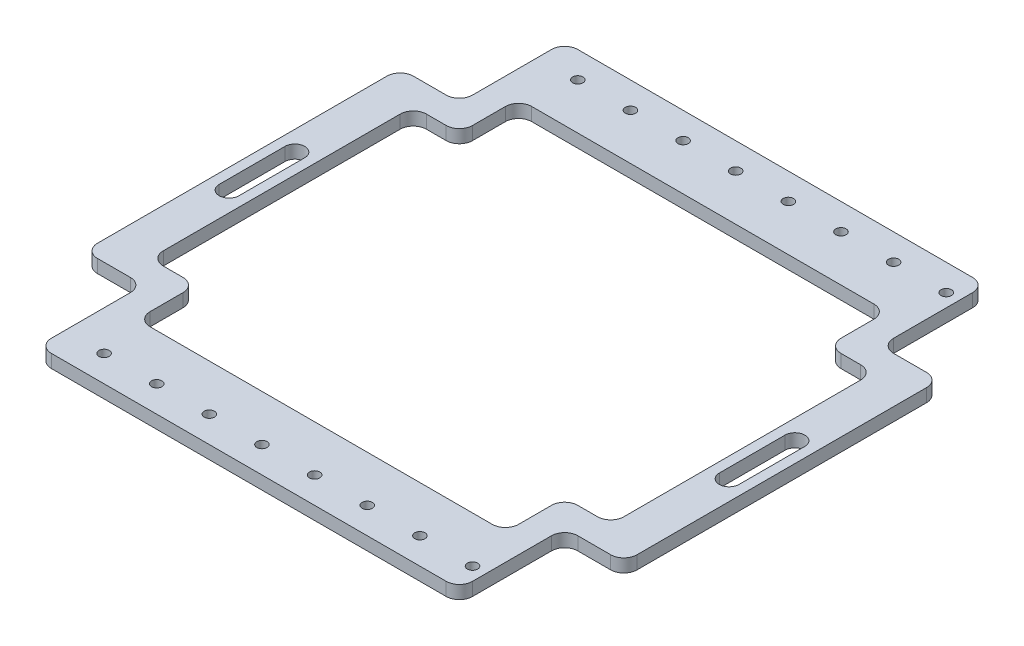
SolidWorks part; units mm, degrees
material "PC High Viscosity"
ref_plane "Front Plane" through (0, 0, 0) normal (0, 0, 1) x (1, 0, 0)
ref_plane "Top Plane" through (0, 0, 0) normal (0, 1, 0) x (1, 0, 0)
ref_plane "Right Plane" through (0, 0, 0) normal (1, 0, 0) x (0, 0, -1)
sketch "Sketch1" plane through (0, 0, 0) normal (0, 1, 0) x (1, 0, 0)
  line L0 (0, 0) -> (0, 50.8)
  line L5 (0, 50.8) -> (-28.575, 50.8)
  line L6 (-28.575, 50.8) -> (-28.575, 203.2)
  line L7 (-28.575, 203.2) -> (0, 203.2)
  line L8 (0, 203.2) -> (0, 254)
  line L9 (0, 254) -> (203.2, 254)
  line L10 (203.2, 254) -> (203.2, 203.2)
  line L11 (203.2, 203.2) -> (231.775, 203.2)
  line L12 (231.775, 203.2) -> (231.775, 50.8)
  line L13 (231.775, 50.8) -> (203.2, 50.8)
  line L14 (203.2, 50.8) -> (203.2, 0)
  line L15 (203.2, 0) -> (0, 0)
  line L16 (101.6, 219.075) -> (101.6, 34.925) construction
  line L17 (12.7, 219.075) -> (190.5, 219.075)
  line L18 (12.7, 219.075) -> (12.7, 34.925)
  line L19 (12.7, 34.925) -> (190.5, 34.925)
  line L20 (190.5, 219.075) -> (190.5, 34.925)
  line L21 (-9.525, 63.5) -> (12.7, 63.5)
  line L22 (-9.525, 63.5) -> (-9.525, 190.5)
  line L23 (-9.525, 190.5) -> (12.7, 190.5)
  line L24 (12.7, 63.5) -> (12.7, 190.5)
  line L25 (212.725, 190.5) -> (190.5, 190.5)
  line L26 (190.5, 63.5) -> (190.5, 190.5)
  line L27 (212.725, 63.5) -> (190.5, 63.5)
  line L28 (212.725, 63.5) -> (212.725, 190.5)
  line L29 (12.7, 127) -> (-9.525, 127) construction
  line L30 (-19.05, 111.125) -> (-19.05, 142.875) construction
  line L31 (-23.8125, 111.125) -> (-23.8125, 142.875)
  line L32 (-14.2875, 111.125) -> (-14.2875, 142.875)
  line L33 (222.25, 111.125) -> (222.25, 142.875) construction
  line L34 (227.0125, 111.125) -> (227.0125, 142.875)
  line L35 (217.4875, 111.125) -> (217.4875, 142.875)
  line L36 (12.7, 219.075) -> (12.7, 254) construction
  line L37 (12.7, 34.925) -> (12.7, 0) construction
  circle A0 centre (196.85, 241.3) radius 2.4892
  circle A1 centre (196.85, 12.7) radius 2.4892
  arc A2 (-23.8125, 111.125) -> (-14.2875, 111.125) centre (-19.05, 111.125) ccw
  arc A3 (-14.2875, 142.875) -> (-23.8125, 142.875) centre (-19.05, 142.875) ccw
  arc A4 (227.0125, 111.125) -> (217.4875, 111.125) centre (222.25, 111.125) cw
  arc A5 (217.4875, 142.875) -> (227.0125, 142.875) centre (222.25, 142.875) cw
  point P34 (-19.05, 127)
  point P44 (222.25, 127)
  dimension "D10" = 4.9784
  dimension "D1" = 177.8
  dimension "D5" = 12.7
  dimension "D6" = 12.7
  dimension "D7" = 152.4
  dimension "D8" = 22.225
  dimension "D9" = 19.05
  dimension "D11" = 12.7
  dimension "D12" = 12.7
  dimension "D13" = 6.35
  dimension "D14" = 12.7
  dimension "D15" = 9.525
  dimension "D16" = 9.525
  dimension "D17" = 31.75
  dimension "D2" = 254
  dimension "D3" = 184.15
extrude "Boss-Extrude1" add sketch "Sketch1" along normal mid plane 6.35 contours L15 L14 L13 L12 L11 L10 L9 L8 L7 L6 L5 L0 A1 A0 L28 L27 L20 L19 L18 L21 L22 L23 L17 L25 region at (3.6373, 0, -25.4)
fillet "Fillet1" radius 6.35 24 edges at (0, 0, 0) (0, 0, -50.8) (-28.575, 0, -50.8) (-28.575, 0, -203.2) (0, 0, -203.2) (0, 0, -254) (203.2, 0, -254) (203.2, 0, -203.2) (231.775, 0, -203.2) (231.775, 0, -50.8) (203.2, 0, -50.8) (203.2, 0, 0) (212.725, 0, -190.5) (190.5, 0, -190.5) (190.5, 0, -219.075) (12.7, 0, -219.075) (-9.525, 0, -190.5) (-9.525, 0, -63.5) (12.7, 0, -63.5) (12.7, 0, -34.925) (190.5, 0, -34.925) (190.5, 0, -63.5) (212.725, 0, -63.5) (12.7, 0, -190.5)
pattern_linear "LPattern1" count 8 spacing 25.4 along (-1, 0, 0) of face at (196.85, 3.175, -238.8108) of face at (196.85, 3.175, -10.2108)
equation "\"D6@Sketch1\"=\"D5@Sketch1\""
equation "\"D14@Sketch1\"=\"D5@Sketch1\""
